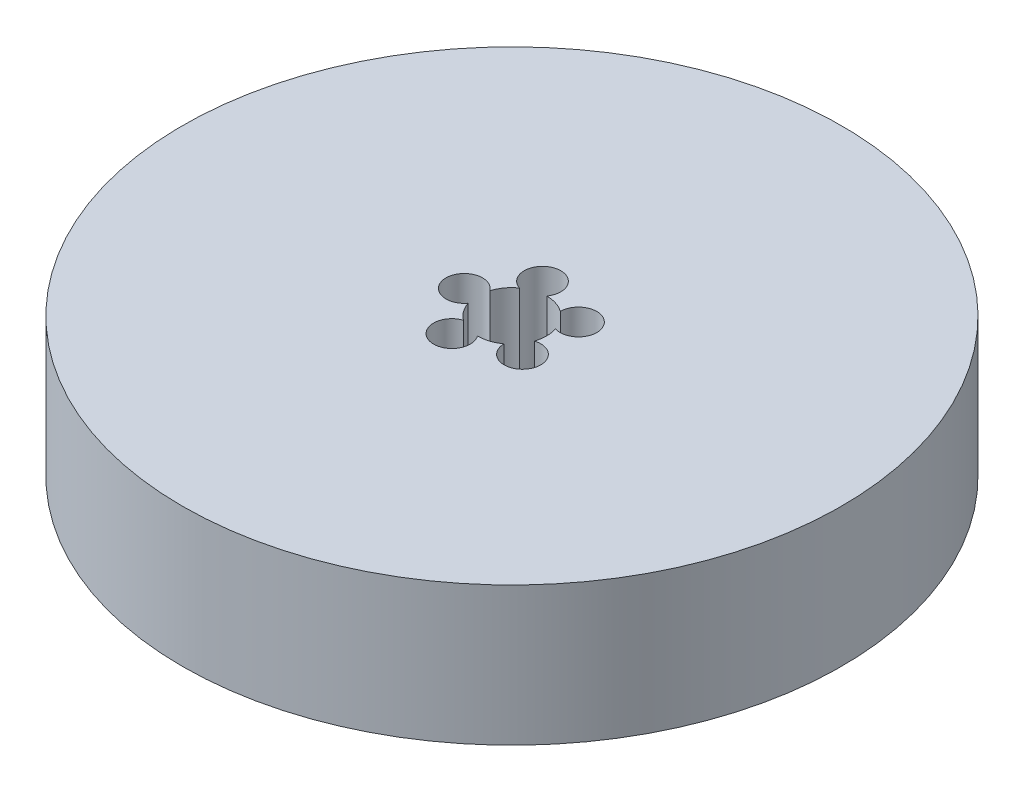
SolidWorks part; units mm, degrees
ref_plane "Front Plane" through (0, 0, 0) normal (0, 0, 1) x (1, 0, 0)
ref_plane "Top Plane" through (0, 0, 0) normal (0, 1, 0) x (1, 0, 0)
ref_plane "Right Plane" through (0, 0, 0) normal (1, 0, 0) x (0, 0, -1)
sketch "Sketch1" plane through (0, 0, 0) normal (0, 1, 0) x (1, 0, 0)
  circle A0 centre (0, 0) radius 47.5
  dimension "FLANGE_OD" = 95
extrude "Boss-Extrude1" add sketch "Sketch1" along normal blind 20
sketch "Sketch2" plane through (0, 0, 0) normal (0, 1, 0) x (1, 0, 0)
  circle A0 centre (0, 0) radius 5
  dimension "BORE_D" = 10
extrude "Cut-Extrude1" cut sketch "Sketch2" along normal through all
sketch "Sketch3" plane through (0, 20, 0) normal (0, 1, 0) x (1, 0, 0)
  circle A0 centre (0, 0) radius 6.8652 construction
  circle A1 centre (-6.8652, 0) radius 2.639
  dimension "BOLT_D" = 5.2779
  dimension "BOLT_PCD" = 13.7305
extrude "Cut-Extrude2" cut sketch "Sketch3" against normal blind 15.7576
pattern_circular "CirPattern1" count 5 over 360 about axis through (0, 0, 0) along (0, 1, 0) of "Cut-Extrude2"
